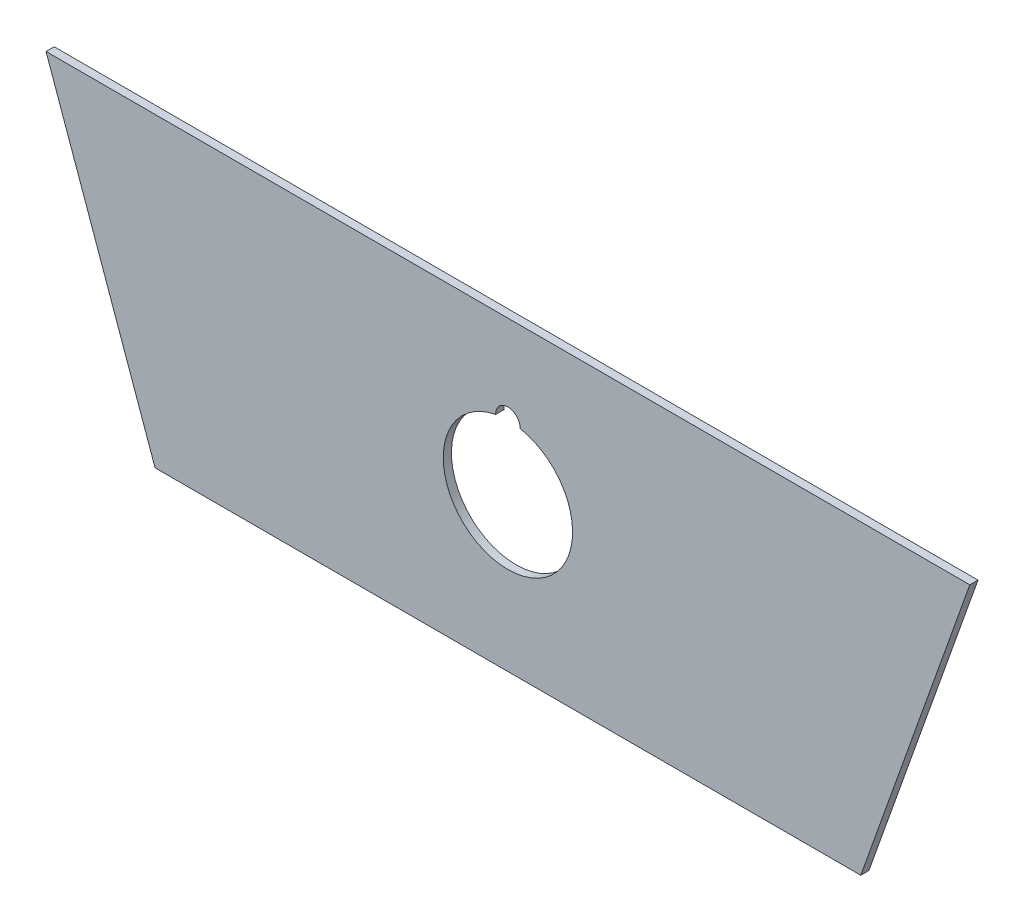
SolidWorks part; units mm, degrees
material "AISI 4130 Steel, annealed at 865C"
ref_plane "Plane1" through (0, 0, 0) normal (0, 0, 1) x (1, 0, 0)
ref_plane "Plane2" through (0, 0, 0) normal (0, 1, 0) x (1, 0, 0)
ref_plane "Plane3" through (0, 0, 0) normal (1, 0, 0) x (0, 0, -1)
ref_axis "Axis1" through (-80.9, 0, 0) along (1, 0, 0)
ref_axis "Axis2" through (0, 0, -80.9) along (0, 0, 1)
ref_axis "Axis3" through (0, 50, 0) along (0, -1, 0)
sketch "Sketch1" plane through (0, 0, 0) normal (0, 0, 1) x (1, 0, 0)
  line L1 (-57.5, -19.05) -> (57.5, -19.05)
  line L2 (-57.5, -19.05) -> (-57.5, 19.05)
  line L3 (-57.5, 19.05) -> (57.5, 19.05)
  line L4 (57.5, -19.05) -> (57.5, 19.05)
  line L5 (-57.5, -19.05) -> (57.5, 19.05) construction
  line L6 (-57.5, 19.05) -> (57.5, -19.05) construction
  point P0 (0, 0)
  dimension "D1" = 38.1
  dimension "D2" = 115
extrude "Boss-Extrude1" add sketch "Sketch1" along normal blind 1.016
sketch "Sketch2" plane through (0, 0, 0) normal (0, 0, 1) x (1, 0, 0)
  line L0 (0, 7.95) -> (0, 0) construction
  line L1 (-57.5, 19.05) -> (-57.5, -19.05) construction
  line L2 (-57.5, 19.05) -> (-57.5, -19.05)
  line L3 (57.5, -19.05) -> (57.5, 19.05) construction
  line L4 (57.5, -19.05) -> (57.5, 19.05)
  line L5 (-57.5, 19.05) -> (-43.922, -19.05)
  line L6 (-57.5, -19.05) -> (57.5, -19.05) construction
  line L7 (-43.922, -19.05) -> (-57.5, -19.05)
  line L8 (57.5, 19.05) -> (43.922, -19.05)
  line L9 (43.922, -19.05) -> (57.5, -19.05)
  arc A0 (-1.5243, 7.9044) -> (1.5243, 7.9044) centre (0, 0) ccw
  arc A1 (1.5243, 7.9044) -> (-1.5243, 7.9044) centre (0, 7.95) ccw
  dimension "D1" = 16.1
  dimension "D2" = 3.05
  dimension "D3" = 7.95
  dimension "D4" = 39.23
extrude "Cut-Extrude2" cut sketch "Sketch2" along normal through all
